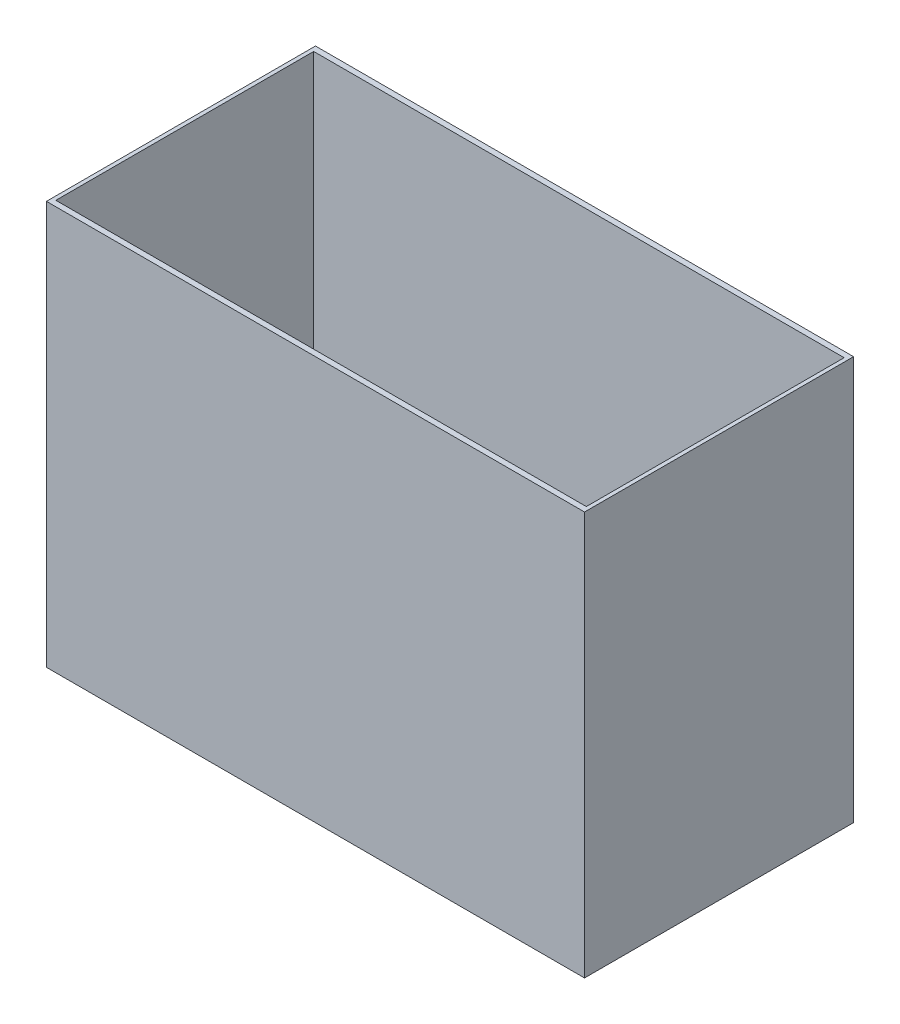
SolidWorks part; units mm, degrees
ref_plane "Front Plane" through (0, 0, 0) normal (0, 0, 1) x (1, 0, 0)
ref_plane "Top Plane" through (0, 0, 0) normal (0, 1, 0) x (1, 0, 0)
ref_plane "Right Plane" through (0, 0, 0) normal (1, 0, 0) x (0, 0, -1)
other "Bounding Box"
ref_plane "Default Plane" through (-292.1, 0, -139.7) normal (0, 1, 0) x (1, 0, 0)
sketch "Sketch1" plane through (0, 0, 0) normal (0, 1, 0) x (1, 0, 0)
  line L0 (-292.1, 0) -> (292.1, 0) construction
  line L1 (-292.1, 139.7) -> (292.1, 139.7)
  line L2 (-292.1, 139.7) -> (-292.1, -139.7)
  line L3 (-292.1, -139.7) -> (292.1, -139.7)
  line L4 (292.1, 139.7) -> (292.1, -139.7)
  line L5 (0, 139.7) -> (0, -139.7) construction
  point P8 (0, 0)
  dimension "D1" = 584.2
  dimension "D2" = 279.4
extrude "Boss-Extrude1" add sketch "Sketch1" along normal blind 12.7
sketch "Sketch2" plane through (0, 12.7, 0) normal (0, 1, 0) x (1, 0, 0)
  line L0 (-245.9259, -63.5) -> (-55.3589, -63.5) construction
  line L1 (-241.3, -120.6497) -> (-152.4, -120.6497)
  line L2 (-241.3, -120.6497) -> (-241.3, -101.5997)
  line L3 (-241.3, -101.5997) -> (-152.4, -101.5997)
  line L4 (-152.4, -120.6497) -> (-152.4, -101.5997)
  line L5 (-241.3, -120.6497) -> (-152.4, -101.5997) construction
  line L6 (-241.3, -101.5997) -> (-152.4, -120.6497) construction
  line L7 (-292.1, 139.7) -> (-292.1, -139.7) construction
  line L8 (-292.1, 0) -> (292.1, 0) construction
  line L9 (292.1, -139.7) -> (292.1, 139.7) construction
  line L10 (0, 0) -> (0, 121.6784) construction
  line L11 (241.3, -101.5997) -> (152.4, -120.6497) construction
  line L12 (241.3, -120.6497) -> (152.4, -101.5997) construction
  line L13 (152.4, -120.6497) -> (152.4, -101.5997)
  line L14 (241.3, -101.5997) -> (152.4, -101.5997)
  line L15 (241.3, -120.6497) -> (241.3, -101.5997)
  line L16 (241.3, -120.6497) -> (152.4, -120.6497)
  point P0 (-196.85, -111.1247)
  point P17 (196.85, -111.1247)
  dimension "D1" = 19.05
  dimension "D2" = 88.9
  dimension "D3" = 38.0997
  dimension "D4" = 50.8
  dimension "D5" = 63.5
extrude "Boss-Extrude2" [suppressed] add sketch "Sketch2" along normal blind 304.8 separate body contours L2 L1 L4 L3
pattern_linear "LPattern1" [suppressed] count 2 spacing 304.8 of bodies 101
pattern_linear "LPattern2" [suppressed] count 2 spacing 215.9 of bodies 101
sketch "Sketch3" plane through (0, 0, 0) normal (0, 1, 0) x (1, 0, 0)
  line L1 (-304.8, -152.4) -> (304.8, -152.4)
  line L2 (-304.8, -152.4) -> (-304.8, 152.4)
  line L3 (-304.8, 152.4) -> (304.8, 152.4)
  line L4 (304.8, -152.4) -> (304.8, 152.4)
  line L5 (-304.8, -152.4) -> (304.8, 152.4) construction
  line L6 (-304.8, 152.4) -> (304.8, -152.4) construction
  line L7 (-300.482, -146.05) -> (300.482, -146.05)
  line L8 (-300.482, -146.05) -> (-300.482, 146.05)
  line L9 (-300.482, 146.05) -> (300.482, 146.05)
  line L10 (300.482, -146.05) -> (300.482, 146.05)
  line L11 (-300.482, -146.05) -> (300.482, 146.05) construction
  line L12 (-300.482, 146.05) -> (300.482, -146.05) construction
  point P0 (0, 0)
  point P6 (0, 0)
  dimension "D1" = 609.6
  dimension "D2" = 304.8
  dimension "D3" = 292.1
  dimension "D4" = 600.964
extrude "Boss-Extrude3" add sketch "Sketch3" along normal blind 457.2 separate body
